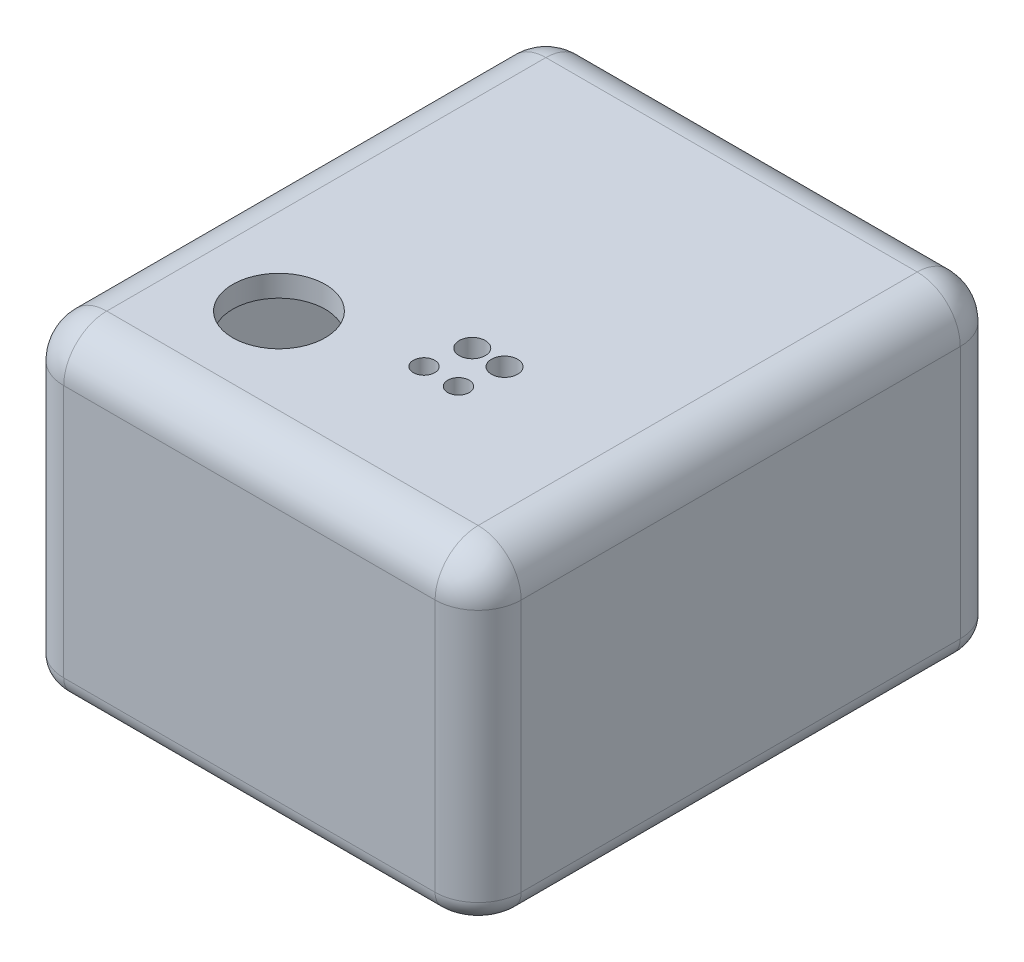
SolidWorks part; units mm, degrees
ref_plane "Front Plane" through (0, 0, 0) normal (0, 0, 1) x (1, 0, 0)
ref_plane "Top Plane" through (0, 0, 0) normal (0, 1, 0) x (1, 0, 0)
ref_plane "Right Plane" through (0, 0, 0) normal (1, 0, 0) x (0, 0, -1)
sketch "Sketch1" plane through (0, 0, 0) normal (0, 1, 0) x (1, 0, 0)
  line L1 (-53.135, -61) -> (53.135, -61)
  line L2 (-53.135, -61) -> (-53.135, 61)
  line L3 (-53.135, 61) -> (53.135, 61)
  line L4 (53.135, -61) -> (53.135, 61)
  line L5 (-53.135, -61) -> (53.135, 61) construction
  line L6 (-53.135, 61) -> (53.135, -61) construction
  point P0 (0, 0)
  dimension "D1" = 106.27
  dimension "D2" = 122
extrude "Boss-Extrude1" add sketch "Sketch1" along normal blind 73.8
sketch "Sketch2" plane through (0, 0, 0) normal (0, -1, 0) x (1, 0, 0)
  line L0 (-53.135, -61) -> (-53.135, 61) construction
  line L1 (-43.135, -51) -> (43.135, -51)
  line L2 (-43.135, -51) -> (-43.135, 51)
  line L3 (-43.135, 51) -> (43.135, 51)
  line L4 (43.135, -51) -> (43.135, 51)
  line L5 (-43.135, -51) -> (43.135, 51) construction
  line L6 (-43.135, 51) -> (43.135, -51) construction
  line L7 (-53.135, 61) -> (53.135, 61) construction
  point P0 (0, 0)
  dimension "D1" = 10
  dimension "D2" = 10
extrude "Cut-Extrude1" cut sketch "Sketch2" against normal blind 68.8
fillet "Fillet1" radius 10 4 edges at (0, 73.8, -61) (53.135, 73.8, 0) (0, 73.8, 61) (-53.135, 73.8, 0)
fillet "Fillet2" radius 10 8 edges at (-53.135, 31.9, -61) (53.135, 31.9, -61) (53.135, 31.9, 61) (-53.135, 31.9, 61) (-50.2061, 70.8711, -58.0711) (50.2061, 70.8711, -58.0711) (50.2061, 70.8711, 58.0711) (-50.2061, 70.8711, 58.0711)
fillet "Fillet3" radius 7.5 4 edges at (43.135, 68.8, 0) (0, 68.8, -51) (-43.135, 68.8, 0) (0, 68.8, 51)
fillet "Fillet4" radius 7.5 8 edges at (43.135, 30.65, 51) (43.135, 30.65, -51) (-43.135, 30.65, -51) (-43.135, 30.65, 51) (40.9383, 66.6033, 48.8033) (40.9383, 66.6033, -48.8033) (-40.9383, 66.6033, -48.8033) (-40.9383, 66.6033, 48.8033)
fillet "Fillet6" radius 5 8 edges at (-50.2061, 0, 58.0711) (-53.135, 0, 0) (-50.2061, 0, -58.0711) (0, 0, -61) (50.2061, 0, -58.0711) (53.135, 0, 0) (50.2061, 0, 58.0711) (0, 0, 61)
sketch "Sketch3" plane through (0, 73.8, 0) normal (0, 1, 0) x (1, 0, 0)
  line L0 (-43.135, -51) -> (43.135, -51) construction
  line L2 (-43.135, 51) -> (-43.135, -51) construction
  circle A0 centre (14.265, -16) radius 3.04
  circle A1 centre (6.765, -16) radius 3.04
  dimension "D1" = 7.5
  dimension "D4" = 6.08
  dimension "D5" = 6.08
  dimension "D2" = 49.9
  dimension "D3" = 35
  dimension "D6" = 35
extrude "Cut-Extrude2" cut sketch "Sketch3" against normal blind 5
sketch "Sketch4" plane through (0, 73.8, 0) normal (0, 1, 0) x (1, 0, 0)
  line L0 (-43.135, 51) -> (-43.135, -51) construction
  line L4 (-43.135, -51) -> (43.135, -51) construction
  circle A0 centre (-23.135, -31) radius 10.75
  dimension "D1" = 21.5
  dimension "D2" = 20
  dimension "D3" = 20
extrude "Cut-Extrude3" cut sketch "Sketch4" against normal blind 5
sketch "Sketch5" plane through (0, 73.8, 0) normal (0, 1, 0) x (1, 0, 0)
  line L2 (-43.135, -51) -> (43.135, -51) construction
  line L3 (-43.135, 51) -> (-43.135, -51) construction
  circle A0 centre (4.865, -25.3) radius 2.5
  circle A1 centre (12.865, -25.3) radius 2.5
  dimension "D1" = 48
  dimension "D5" = 5
  dimension "D6" = 5
  dimension "D2" = 8
  dimension "D3" = 25.7
  dimension "D4" = 25.7
extrude "Cut-Extrude4" cut sketch "Sketch5" against normal blind 5
hole_wizard "#4-40 Tapped Hole3" positions "Sketch15" profile "Sketch16" tap size "#4-40" standard "ANSI Inch"
sketch "Sketch15" plane through (100.4121, -2, -32.7024) normal (0, -1, 0) x (-1, 0, 0)
  point P0 (143.5471, -83.7024)
sketch "Sketch16" plane through (-43.135, -2, 51) normal (1, 0, 0) x (0, 0, -1)
  line L0 (0, 0) -> (0, 30.6792)
  line L1 (0, 30.6792) -> (1.1303, 30)
  line L2 (1.1303, 30) -> (1.1303, 0.7779)
  line L3 (1.1303, 0.7779) -> (2.0574, 0)
  line L4 (2.0574, 0) -> (0, 0)
  line L5 (-1.1303, 0.7779) -> (-2.0574, 0) construction
  line L6 (0, 30.6792) -> (-1.1303, 30) construction
  line L7 (0, -6.35) -> (0, 107.95) construction
  dimension "Tap Drill Dia." = 2.2606
  dimension "Tap Drill Depth" = 30
  dimension "Near C'Sink Dia." = 4.1148
  dimension "Near C'Sink Angle" = 100
  dimension "Drill Angle" = 118
cosmetic thread "Hole Thread4" parameters "D1"=5.69, "D2"=2.8448
hole_wizard "#4-40 Tapped Hole4" positions "Sketch17" profile "Sketch18" tap size "#4-40" standard "ANSI Inch"
sketch "Sketch17" plane through (100.4121, -2, -32.7024) normal (0, -1, 0) x (-1, 0, 0)
  point P0 (57.2771, 18.2976)
sketch "Sketch18" plane through (43.135, -2, -51) normal (1, 0, 0) x (0, 0, -1)
  line L0 (0, 0) -> (0, 30.6792)
  line L1 (0, 30.6792) -> (1.1303, 30)
  line L2 (1.1303, 30) -> (1.1303, 0.7779)
  line L3 (1.1303, 0.7779) -> (2.0574, 0)
  line L4 (2.0574, 0) -> (0, 0)
  line L5 (-1.1303, 0.7779) -> (-2.0574, 0) construction
  line L6 (0, 30.6792) -> (-1.1303, 30) construction
  line L7 (0, -6.35) -> (0, 107.95) construction
  dimension "Tap Drill Dia." = 2.2606
  dimension "Tap Drill Depth" = 30
  dimension "Near C'Sink Dia." = 4.1148
  dimension "Near C'Sink Angle" = 100
  dimension "Drill Angle" = 118
cosmetic thread "Hole Thread5" parameters "D1"=5.69, "D2"=2.8448
equation "\"D1@Boss-Extrude1\"=\"topDepth\""
equation "\"topDepth\"=73.8"
equation "\"D1@Cut-Extrude1\"=\"topDepth\"-5"
